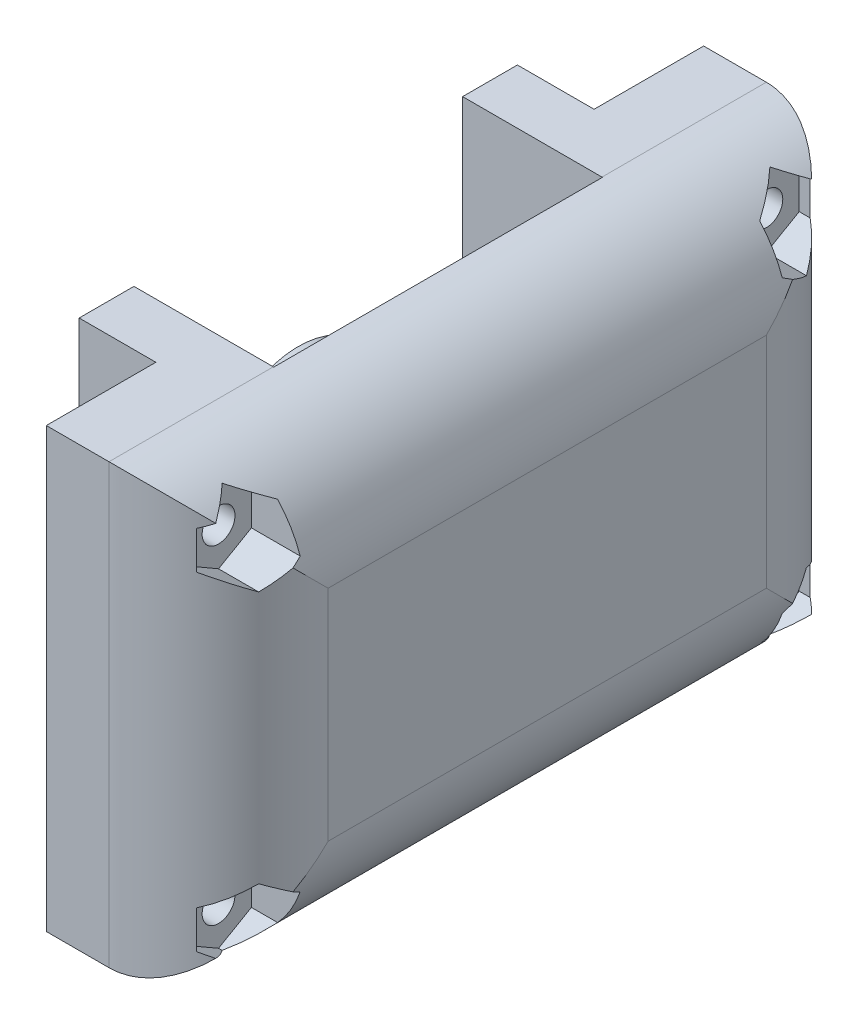
SolidWorks part; units mm, degrees
ref_plane "Alzado" through (0, 0, 0) normal (0, 0, 1) x (1, 0, 0)
ref_plane "Planta" through (0, 0, 0) normal (0, 1, 0) x (1, 0, 0)
ref_plane "Vista lateral" through (0, 0, 0) normal (1, 0, 0) x (0, 0, -1)
sketch "Croquis1" plane through (0, 0, 0) normal (1, 0, 0) x (0, 0, -1)
  line L0 (0, 0) -> (0, 16.1453) construction
  line L1 (-30, -20) -> (30, -20)
  line L2 (-30, -20) -> (-30, 20)
  line L3 (-30, 20) -> (30, 20)
  line L4 (30, -20) -> (30, 20)
  line L5 (-30, -20) -> (30, 20) construction
  line L6 (-30, 20) -> (30, -20) construction
  line L7 (0, 0) -> (-19.1227, 0) construction
  circle A0 centre (-25, 15) radius 1.5
  circle A1 centre (25, 15) radius 1.5
  circle A2 centre (25, -15) radius 1.5
  circle A3 centre (-25, -15) radius 1.5
  point P0 (0, 0)
  dimension "D3" = 3
  dimension "D1" = 60
  dimension "D2" = 40
  dimension "D4" = 5
  dimension "D5" = 5
extrude "Saliente-Extruir1" add sketch "Croquis1" along normal blind 17.96
sketch "Croquis3" plane through (0, 0, 0) normal (-1, 0, 0) x (0, 0, 1)
  line L0 (30, -20) -> (-30, -20) construction
  line L1 (-30, 20) -> (-15, 20)
  line L2 (-30, 20) -> (-30, -20)
  line L3 (-30, -20) -> (-15, -20)
  line L4 (-15, 20) -> (-15, -20)
  line L5 (0, 0) -> (0, -20) construction
  line L6 (30, -20) -> (15, -20)
  line L7 (15, 20) -> (15, -20)
  line L8 (30, 20) -> (15, 20)
  line L9 (30, 20) -> (30, -20)
  circle A0 centre (25, -15) radius 1.5 construction
  circle A1 centre (25, 15) radius 1.5 construction
  circle A2 centre (-25, -15) radius 1.5 construction
  circle A3 centre (-25, 15) radius 1.5 construction
  circle A4 centre (25, -15) radius 1.5
  circle A5 centre (25, 15) radius 1.5
  circle A6 centre (-25, -15) radius 1.5
  circle A7 centre (-25, 15) radius 1.5
  dimension "D1" = 30
extrude "Saliente-Extruir2" add sketch "Croquis3" along normal blind 4.7625
sketch "Croquis4" plane through (0, 0, 0) normal (-1, 0, 0) x (0, 0, 1)
  circle A2 centre (0, 0) radius 7.75
  dimension "D1" = 15.5
extrude "Saliente-Extruir3" add sketch "Croquis4" along normal blind 4.7625
fillet "Redondeo2" radius 10 4 edges at (17.96, 0, -30) (17.96, 20, 0) (17.96, -20, 0) (17.96, 0, 30)
sketch "Croquis5" plane through (17.96, 0, 0) normal (1, 0, 0) x (0, 0, -1)
  line L1 (-25, 18.4641) -> (-28, 16.7321)
  line L2 (-28, 16.7321) -> (-28, 13.2679)
  line L3 (-28, 13.2679) -> (-25, 11.5359)
  line L4 (-25, 11.5359) -> (-22, 13.2679)
  line L5 (-22, 13.2679) -> (-22, 16.7321)
  line L6 (-22, 16.7321) -> (-25, 18.4641)
  line L7 (25, 18.4641) -> (22, 16.7321)
  line L8 (22, 16.7321) -> (22, 13.2679)
  line L9 (22, 13.2679) -> (25, 11.5359)
  line L10 (25, 11.5359) -> (28, 13.2679)
  line L11 (28, 13.2679) -> (28, 16.7321)
  line L12 (28, 16.7321) -> (25, 18.4641)
  line L13 (25, -18.4641) -> (28, -16.7321)
  line L14 (28, -16.7321) -> (28, -13.2679)
  line L15 (28, -13.2679) -> (25, -11.5359)
  line L16 (25, -11.5359) -> (22, -13.2679)
  line L17 (22, -13.2679) -> (22, -16.7321)
  line L18 (22, -16.7321) -> (25, -18.4641)
  line L19 (-25, -18.4641) -> (-22, -16.7321)
  line L20 (-22, -16.7321) -> (-22, -13.2679)
  line L21 (-22, -13.2679) -> (-25, -11.5359)
  line L22 (-25, -11.5359) -> (-28, -13.2679)
  line L23 (-28, -13.2679) -> (-28, -16.7321)
  line L24 (-28, -16.7321) -> (-25, -18.4641)
  circle A0 centre (-25, 15) radius 3 construction
  circle A1 centre (25, 15) radius 3 construction
  circle A2 centre (25, -15) radius 3 construction
  circle A3 centre (-25, -15) radius 3 construction
  dimension "D1" = 6
  dimension "D2" = 6
  dimension "D3" = 6
  dimension "D4" = 6
extrude "Cortar-Extruir1" cut sketch "Croquis5" against normal blind 5
sketch "Croquis6" plane through (-4.7625, 0, 0) normal (-1, 0, 0) x (0, 0, 1)
  line L0 (15, -20) -> (30, -20) construction
  line L1 (30, 20) -> (20, 20)
  line L2 (30, 20) -> (30, -20)
  line L3 (30, -20) -> (20, -20)
  line L4 (20, 20) -> (20, -20)
  line L5 (-30, -20) -> (-15, -20) construction
  line L6 (-30, 20) -> (-20, 20)
  line L7 (-30, 20) -> (-30, -20)
  line L8 (-30, -20) -> (-20, -20)
  line L9 (-20, 20) -> (-20, -20)
  line L10 (-25, 15) -> (-30, 15) construction
  dimension "D1" = 10
  dimension "D2" = 10
extrude "Cortar-Extruir2" cut sketch "Croquis6" against normal blind 7
sketch "Croquis7" plane through (0, 0, 0) normal (-1, 0, 0) x (0, 0, 1)
  line L4 (-15, -20) -> (15, -20)
  line L5 (15, -20) -> (15, 20)
  line L6 (15, 20) -> (-15, 20)
  line L7 (-15, 20) -> (-15, -20)
  line L8 (-15, -20) -> (15, -20)
  line L9 (15, -20) -> (15, 20)
  line L10 (15, 20) -> (-15, 20)
  line L11 (-15, 20) -> (-15, -20)
  circle A1 centre (0, 0) radius 7.75
  circle A2 centre (0, 0) radius 7.75
  dimension "D1" = 0
  dimension "D2" = 0
extrude "Cortar-Extruir3" cut sketch "Croquis7" against normal blind 8
